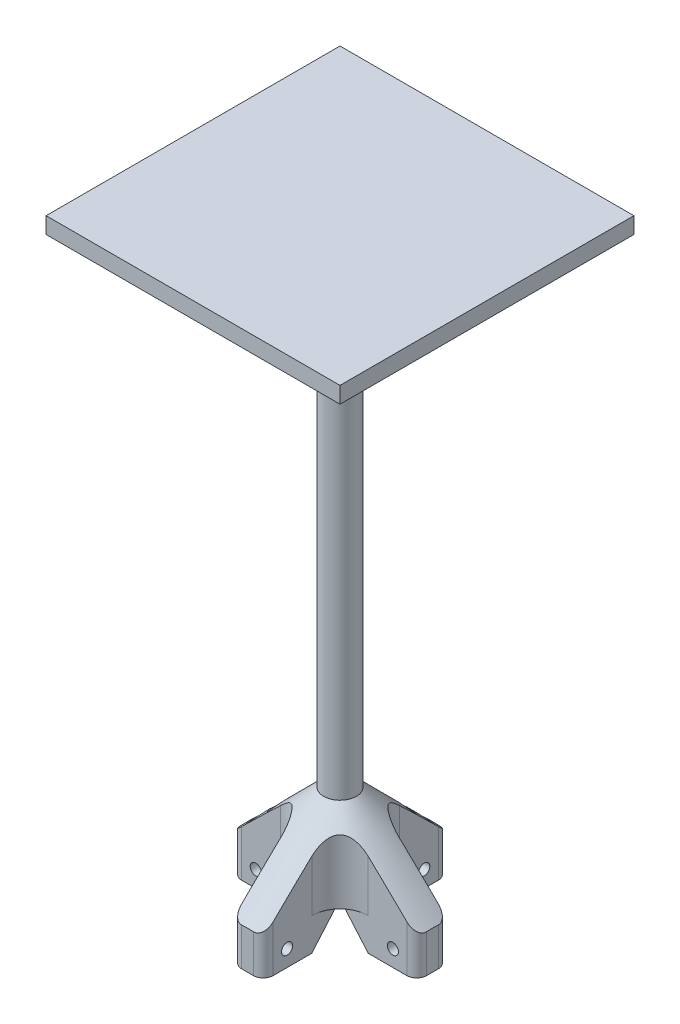
SolidWorks part; units mm, degrees
ref_plane "Front Plane" through (0, 0, 0) normal (0, 0, 1) x (1, 0, 0)
ref_plane "Top Plane" through (0, 0, 0) normal (0, 1, 0) x (1, 0, 0)
ref_plane "Right Plane" through (0, 0, 0) normal (1, 0, 0) x (0, 0, -1)
sketch "Sketch8" plane through (0, 0, 0) normal (0, 1, 0) x (1, 0, 0)
  line L0 (13.7, 4.8) -> (28.3, 4.8)
  line L1 (-4.8, 13.7) -> (4.8, 13.7)
  line L2 (-4.8, 13.7) -> (-4.8, 28.3)
  line L3 (-4.8, 28.3) -> (4.8, 28.3)
  line L4 (4.8, 13.7) -> (4.8, 28.3)
  line L5 (-4.8, 13.7) -> (4.8, 28.3) construction
  line L6 (-4.8, 28.3) -> (4.8, 13.7) construction
  line L7 (13.7, 4.8) -> (13.7, -4.8)
  line L8 (13.7, -4.8) -> (28.3, -4.8)
  line L9 (28.3, 4.8) -> (28.3, -4.8)
  line L10 (4.8, -13.7) -> (4.8, -28.3)
  line L11 (4.8, -13.7) -> (-4.8, -13.7)
  line L12 (-4.8, -13.7) -> (-4.8, -28.3)
  line L13 (4.8, -28.3) -> (-4.8, -28.3)
  line L14 (-13.7, -4.8) -> (-28.3, -4.8)
  line L15 (-13.7, -4.8) -> (-13.7, 4.8)
  line L16 (-13.7, 4.8) -> (-28.3, 4.8)
  line L17 (-28.3, -4.8) -> (-28.3, 4.8)
  line L18 (-13.7, 4.8) -> (0, 4.8)
  line L19 (-13.7, -4.8) -> (0, -4.8)
  line L20 (4.8, 13.7) -> (4.8, 0)
  line L21 (-4.8, 13.7) -> (-4.8, 0)
  line L22 (13.7, -4.8) -> (0, -4.8)
  line L23 (13.7, 4.8) -> (0, 4.8)
  line L24 (-4.8, -13.7) -> (-4.8, 0)
  line L25 (4.8, -13.7) -> (4.8, 0)
  point P0 (0, 21)
  point P21 (0, 0)
  point P38 (0, 0)
  dimension "D1" = 21
  dimension "D2" = 9.6
  dimension "D3" = 4
  dimension "D5" = 14.6
  dimension "D4" = 4
extrude "Boss-Extrude4" add sketch "Sketch8" along normal blind 1.5 separate body contours L17 L14 L15 L16 | L1 L4 L3 L2 | L9 L0 L7 L8 | L13 L10 L11 L12 | L19 L24 L21 L18 L15 | L23 L20 L1 L21 L18 | L25 L22 L7 L23 L20 | L11 L25 L22 L19 L24 | L24 L19 | L18 L21 | L20 L23 | L22 L25 region at (21, 0, 0) region at (9.25, 0, 0) region at (0, 0, -9.25) region at (0, 0, 0) region at (0, 0, 9.25) region at (0, 0, -21) region at (0, 0, 21) region at (-9.25, 0, 0) region at (-21, 0, 0)
sketch "Sketch7" plane through (0, 1.5, 0) normal (0, 1, 0) x (1, 0, 0)
  circle A0 centre (0, 0) radius 5
  dimension "D1" = 10
extrude "Boss-Extrude3" add sketch "Sketch7" along normal blind 170
fillet "Fillet3" radius 8.65 4 edges at (4.8, 0.75, -4.8) (4.8, 0.75, 4.8) (-4.8, 0.75, 4.8) (-4.8, 0.75, -4.8)
sketch "Sketch13" plane through (0, 0, 0) normal (0, -1, 0) x (1, 0, 0)
  line L0 (-4.8, -28.3) -> (-4.8, -13.45) construction
  line L1 (-4.8, -28.3) -> (4.8, -28.3) construction
  line L2 (-4.8, -28.3) -> (-4.8, -13.45)
  line L3 (-4.8, -28.3) -> (4.8, -28.3)
  line L4 (4.8, -28.3) -> (4.8, -13.45) construction
  line L5 (-4.8, -28.3) -> (4.8, -28.3)
  line L6 (-4.8, -28.3) -> (-4.8, -13.45)
  line L7 (-4.8, -13.45) -> (4.8, -13.45)
  line L8 (4.8, -28.3) -> (4.8, -13.45)
  line L9 (-28.3, 4.8) -> (-13.45, 4.8)
  line L10 (-28.3, 4.8) -> (-28.3, -4.8)
  line L11 (-28.3, -4.8) -> (-13.45, -4.8)
  line L12 (-13.45, 4.8) -> (-13.45, -4.8)
  line L13 (4.8, 28.3) -> (4.8, 13.45)
  line L14 (4.8, 28.3) -> (-4.8, 28.3)
  line L15 (-4.8, 28.3) -> (-4.8, 13.45)
  line L16 (4.8, 13.45) -> (-4.8, 13.45)
  line L17 (28.3, -4.8) -> (13.45, -4.8)
  line L18 (28.3, -4.8) -> (28.3, 4.8)
  line L19 (28.3, 4.8) -> (13.45, 4.8)
  line L20 (13.45, -4.8) -> (13.45, 4.8)
  point P21 (0, 0)
  line M10 (-28.3, 4.8) -> (-28.3, -4.8)
  line M11 (-28.3, -4.8) -> (-13.45, -4.8)
  line M14 (-4.8, -28.3) -> (4.8, -28.3)
  line M15 (4.8, -28.3) -> (4.8, -13.45)
  line M17 (13.45, -4.8) -> (28.3, -4.8)
  line M18 (28.3, -4.8) -> (28.3, 4.8)
  line M19 (28.3, 4.8) -> (13.45, 4.8)
  line M21 (4.8, 13.45) -> (4.8, 28.3)
  line M22 (4.8, 28.3) -> (-4.8, 28.3)
  line M23 (-4.8, 28.3) -> (-4.8, 13.45)
  line M25 (-13.45, 4.8) -> (-28.3, 4.8)
  dimension "D1" = 14.85
  dimension "D2" = 4
extrude "Boss-Extrude7" add sketch "Sketch13" along normal blind 10 contours L7 L2 M14 M15 | L12 M25 M10 M11 | L16 M21 M22 M23 | L20 M17 M18 M19 region at (0, 0, -20.875) region at (-20.875, 0, 0) region at (0, 0, 20.875) region at (20.875, 0, 0)
hole_wizard "M3 Clearance Hole2" positions "Sketch9" profile "Sketch10" hole size "M3" standard "ANSI Metric" end condition up to next
sketch "Sketch9" plane through (-4.8, 2.575, 0) normal (1, 0, 0) x (0, -1, 0)
  line L2 (1.075, -4.8) -> (1.075, 4.8) construction
  line L3 (1.075, 5) -> (1.075, -5) construction
  line L4 (1.075, 5) -> (1.075, -5)
  line L7 (12.575, 13.45) -> (2.575, 13.45) construction
  line L8 (12.575, 13.45) -> (2.575, 13.45)
  point P15 (1.075, 0)
  point P38 (7.575, 21)
  point P45 (7.575, 13.45)
  dimension "D1" = 21
sketch "Sketch10" plane through (-4.8, -5, -21) normal (0, 1, 0) x (0, 0, 1)
  line L0 (0, 0) -> (0, 9.601)
  line L1 (0, 9.601) -> (1.7, 9.601)
  line L2 (1.7, 9.601) -> (1.7, 0)
  line L5 (1.7, 0) -> (0, 0)
  line L11 (0, -6.35) -> (0, 107.95) construction
  dimension "Thru Hole Dia." = 3.4
  dimension "Thru Hole Depth" = 9.601
pattern_circular "CirPattern1" count 4 over 360 about axis through (0, 171.5, 0) along (0, -1, 0) of "M3 Clearance Hole2" reverse direction yes
fillet "Fillet8" radius 3 8 edges at (4.8, -4.25, -28.3) (-4.8, -4.25, -28.3) (28.3, -4.25, -4.8) (28.3, -4.25, 4.8) (4.8, -4.25, 28.3) (-4.8, -4.25, 28.3) (-28.3, -4.25, 4.8) (-28.3, -4.25, -4.8)
sketch "Sketch11" plane through (0, 171.5, 0) normal (0, 1, 0) x (1, 0, 0)
  line L1 (-45, 45) -> (45, 45)
  line L2 (-45, 45) -> (-45, -45)
  line L3 (-45, -45) -> (45, -45)
  line L4 (45, 45) -> (45, -45)
  line L5 (-45, 45) -> (45, -45) construction
  line L6 (-45, -45) -> (45, 45) construction
  point P0 (0, 0)
  dimension "D1" = 90
extrude "Boss-Extrude5" add sketch "Sketch11" along normal blind 5
chamfer "Chamfer1" distance 23.5 angle 45 1 edges at (0, 1.5, 5)
fillet "Fillet5" radius 20 1 edges at (0, 171.5, 5)
chamfer "Chamfer2" distance 10 distance2 8.6 4 edges at (13.45, 0, 0) (0, 0, 13.45) (-13.45, 0, 0) (0, 0, -13.45) first distance on face at (13.45, -5, 0) first distance on face at (0, -5, 13.45) first distance on face at (-13.45, -5, 0) first distance on face at (0, -5, -13.45)
